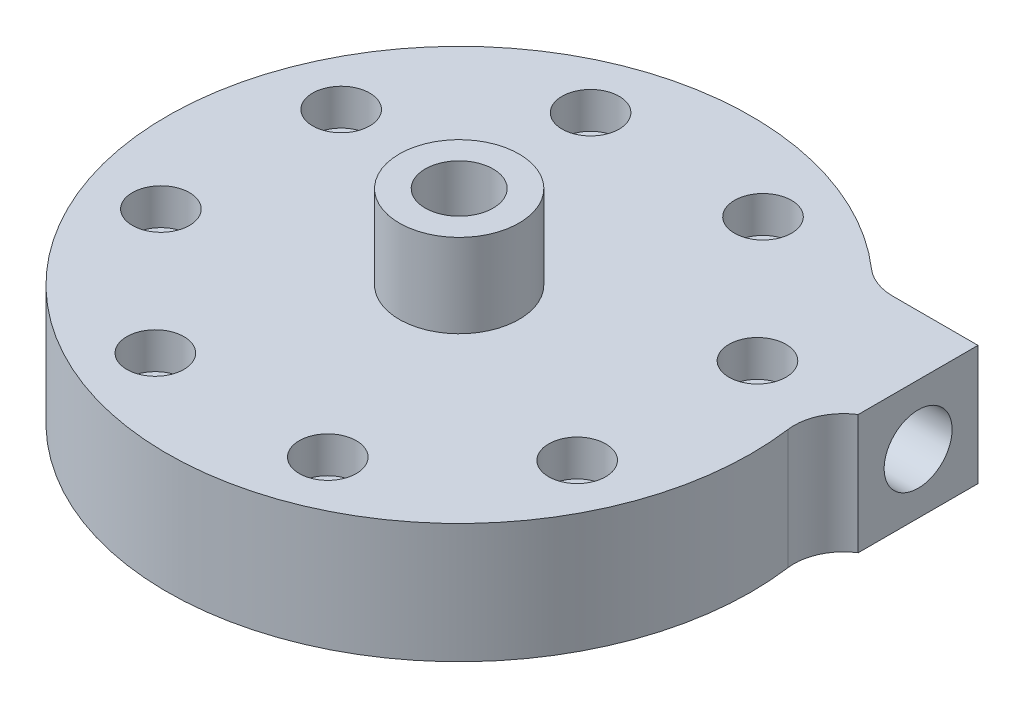
SolidWorks part; units mm, degrees
material "1060 Alloy"
ref_plane "Front" through (0, 0, 0) normal (0, 0, 1) x (1, 0, 0)
ref_plane "Top" through (0, 0, 0) normal (0, 1, 0) x (1, 0, 0)
ref_plane "Right" through (0, 0, 0) normal (1, 0, 0) x (0, 0, -1)
sketch "Sketch1" plane through (0, 0, 0) normal (0, 1, 0) x (1, 0, 0)
  line L0 (0, 0) -> (2.6731, 30.5538) construction
  line L1 (21.117, 30.6705) -> (50.1264, 33.2085) construction
  line L2 (11.6189, 28.3845) -> (50.1264, 28.3845) construction
  line L3 (21.117, 26.0945) -> (50.1264, 23.5565) construction
  line L4 (0, 0) -> (56.1418, -4.9118) construction
  line L5 (21.117, 30.6705) -> (21.117, 28.3845) construction
  line L6 (21.117, 28.3845) -> (21.117, 26.0945) construction
  line L7 (50.1264, 28.3845) -> (50.1264, 33.2085) construction
  line L8 (50.1264, 28.3845) -> (50.1264, 23.5565) construction
  line L9 (60.1264, 28.3845) -> (60.1264, 39.9329)
  line L10 (60.1264, 34.9329) -> (50.1264, 34.9329) construction
  line L11 (60.1264, 34.9329) -> (60.1264, 21.8361) construction
  line L12 (60.1264, 21.8361) -> (50.1264, 21.8361) construction
  line L13 (50.1264, 34.9329) -> (50.1264, 21.8361) construction
  line L14 (60.1264, 39.9329) -> (43.7019, 39.9329)
  line L15 (60.1264, 28.3845) -> (60.1264, 16.8361)
  line L17 (21.117, 30.6705) -> (0, 30.6705) construction
  line L18 (21.117, 26.0945) -> (16.117, 26.0945) construction
  arc A0 (37.1159, 42.408) -> (55.8478, 7.5534) centre (0, 0) ccw
  circle A1 centre (0, 0) radius 30.6705 construction
  arc A2 (55.8478, 7.5534) -> (60.1264, 16.8361) centre (65.2868, 8.8301) cw
  arc A3 (43.7019, 39.9329) -> (37.1159, 42.408) centre (43.7019, 49.9329) cw
  dimension "D1" = 112.7125
  dimension "D2" = 61.341
  dimension "D13" = 9.525
  dimension "D4" = 2.286
  dimension "D3" = 2.29
  dimension "D5" = 5
  dimension "D6" = 5
  dimension "D7" = 5
  dimension "D8" = 9.652
  dimension "D9" = 13.0969
  dimension "D10" = 10
  dimension "D11" = 5
  dimension "D14" = 5
  dimension "D12" = 5
extrude "main body" add sketch "Sketch1" along normal blind 23.0969
ref_plane "body midsection" through (0, 11.5484, 0) normal (0, 1, 0) x (1, 0, 0)
sketch "Sketch7" plane through (0, 23.0969, 0) normal (0, 1, 0) x (1, 0, 0)
  circle A0 centre (0, 0) radius 25.4
  dimension "D1" = 50.8
extrude "inlet boss" add sketch "Sketch7" along normal blind 50.8
sketch "Sketch3" plane through (0, 11.5484, 0) normal (0, 1, 0) x (1, 0, 0)
  line L0 (21.117, 30.6705) -> (0, 30.6705)
  line L1 (0, 30.6705) -> (0, 28.3845)
  line L2 (50.1264, 28.3845) -> (2.4833, 28.3845)
  line L3 (0, 0) -> (2.6731, 30.5538) construction
  line L4 (0, 28.3845) -> (2.4833, 28.3845)
  line L5 (50.1264, 33.2085) -> (50.1264, 34.9329)
  line L6 (50.1264, 34.9329) -> (60.1264, 34.9329)
  line L7 (60.1264, 34.9329) -> (60.1264, 28.3845)
  line L8 (60.1264, 28.3845) -> (50.1264, 28.3845)
  line L9 (21.117, 30.6705) -> (50.1264, 33.2085)
revolve "expansion cone and outlet" cut sketch "Sketch3" angle 360 about L2
sketch "Sketch2" plane through (0, 0, 0) normal (0, 0, 1) x (1, 0, 0)
  line L0 (-56.3562, 11.5484) -> (56.3562, 11.5484) construction
  line L1 (-56.3562, 23.0969) -> (-56.3562, 0) construction
  line L2 (56.3562, 0) -> (56.3562, 23.0969) construction
  line L3 (0, 0) -> (0, 23.0969) construction
  line L4 (25.4, 23.0969) -> (-25.4, 23.0969) construction
  line L5 (0, 18.6817) -> (0, 9.0936)
  line L6 (0, 9.0936) -> (26.67, 9.0936) construction
  line L7 (5.461, 18.6817) -> (5.565, 19.1708) construction
  line L8 (26.67, 14.1736) -> (5.461, 14.1736) construction
  line L9 (26.67, 9.0936) -> (26.67, 14.1736) construction
  line L10 (0, 19.1929) -> (0, 39.1929)
  line L11 (26.67, 14.1736) -> (5.461, 18.6817) construction
  line L12 (5.461, 18.6817) -> (0, 18.6817) construction
  line L13 (5.461, 18.6817) -> (5.461, 9.0936) construction
  line L14 (0, 9.0936) -> (0, 7.0936) construction
  line L15 (0, 7.0936) -> (26.67, 7.0936) construction
  line L16 (26.67, 7.0936) -> (26.67, 9.0936) construction
  line L17 (0, 9.0936) -> (0, 6.5936)
  line L18 (0, 7.0936) -> (0, 6.5936) construction
  line L19 (0, 6.5936) -> (26.67, 6.5936) construction
  line L20 (26.67, 6.5936) -> (26.67, 7.0936) construction
  line L21 (26.67, 6.5936) -> (30.6705, 6.5936) construction
  line L22 (30.6705, 6.5936) -> (30.6705, 13.3233)
  line L23 (26.67, 14.1736) -> (30.6705, 13.3233) construction
  line L24 (5.461, 18.6817) -> (5.461, 19.1929) construction
  line L25 (5.461, 19.1929) -> (0, 19.1929) construction
  line L26 (0, 19.1929) -> (0, 18.6817)
  line L27 (30.6705, 13.3233) -> (30.6705, 13.8344)
  line L28 (30.6705, 13.8344) -> (5.461, 19.1929)
  line L29 (0, 6.5936) -> (0, 0)
  line L30 (0, 0) -> (30.6705, 0)
  line L31 (-56.3562, 0) -> (56.3562, 0) construction
  line L32 (30.6705, 0) -> (30.6705, 6.5936)
  line L33 (30.6705, 13.8344) -> (0, 13.8344) construction
  line L34 (21.117, 13.8344) -> (0, 13.8344) construction
  line L35 (0, 39.1929) -> (6.5484, 39.1929) construction
  line L36 (6.5484, 39.1929) -> (6.5484, 29.1929)
  line L37 (6.5484, 29.1929) -> (5.461, 29.1929)
  line L38 (5.461, 29.1929) -> (5.461, 19.1929)
  line L39 (0, 39.1929) -> (0, 73.8969)
  line L40 (0, 73.8969) -> (25.4, 73.8969)
  line L41 (6.5484, 39.1929) -> (11.5484, 39.1929)
  line L42 (25.4, 73.8969) -> (-25.4, 73.8969) construction
  line L44 (11.5484, 39.1929) -> (11.5484, 23.0969)
  line L46 (25.4, 73.8969) -> (25.4, 23.0969)
  line L47 (25.4, 23.0969) -> (11.5484, 23.0969)
  dimension "D10" = 10
  dimension "D12" = 5
  dimension "D1" = 5.461
  dimension "D2" = 26.67
  dimension "D3" = 9.5881
  dimension "D4" = 5.08
  dimension "D5" = 2
  dimension "D6" = 4.0005
  dimension "D8" = 0.5
  dimension "D9" = 10
  dimension "D11" = 6.5484
revolve "main chamber" cut sketch "Sketch2" angle 360 about L5
sketch "Sketch5" plane through (0, 23.0969, 0) normal (0, 1, 0) x (1, 0, 0)
  line L1 (17.9206, 40.6775) -> (41.4351, 16.0915) construction
  line L3 (11.6189, 28.3845) -> (50.1264, 28.3845) construction
  circle A0 centre (0, 0) radius 44.45 construction
  circle A1 centre (41.4351, 16.0915) radius 2.9766
  circle A2 centre (0, 0) radius 44.45 construction
  circle A3 centre (40.6775, -17.9206) radius 2.9766
  circle A4 centre (0, 0) radius 44.45 construction
  circle A5 centre (16.0915, -41.4351) radius 2.9766
  circle A6 centre (0, 0) radius 44.45 construction
  circle A7 centre (-17.9206, -40.6775) radius 2.9766
  circle A8 centre (0, 0) radius 44.45 construction
  circle A9 centre (-41.4351, -16.0915) radius 2.9766
  circle A10 centre (0, 0) radius 44.45 construction
  circle A11 centre (-40.6775, 17.9206) radius 2.9766
  circle A12 centre (0, 0) radius 44.45 construction
  circle A13 centre (-16.0915, 41.4351) radius 2.9766
  circle A14 centre (0, 0) radius 44.45 construction
  circle A15 centre (17.9206, 40.6775) radius 2.9766
  point P5 (29.6778, 28.3845)
  point P30 (0, 0)
  dimension "D1" = 88.9
  dimension "D2" = 5.9531
  dimension "D4" = 8
sketch "Sketch6" plane through (0, 23.0969, 0) normal (0, 1, 0) x (1, 0, 0)
  circle A0 centre (41.4351, 16.0915) radius 5.5
  circle A1 centre (40.6775, -17.9206) radius 5.5
  circle A2 centre (16.0915, -41.4351) radius 5.5
  circle A3 centre (-17.9206, -40.6775) radius 5.5
  circle A4 centre (-41.4351, -16.0915) radius 5.5
  circle A5 centre (-40.6775, 17.9206) radius 5.5
  circle A6 centre (-16.0915, 41.4351) radius 5.5
  circle A7 centre (17.9206, 40.6775) radius 5.5
  point P19 (0, 0)
  dimension "D1" = 11
  dimension "D2" = 8
ref_plane "exit axial plane" through (0, 0, -28.3845) normal (0, 0, -1) x (-1, 0, 0)
extrude "bolt clearances" cut sketch "Sketch5" against normal through all
extrude "bolt head clearance" cut sketch "Sketch6" against normal blind 7
equation "\"bearing OD\"= 30mm"
equation "\"bearing ID\"= 10mm"
equation "\"bearing depth\"= 9mm"
equation "\"bearing outer race thickness\"= 1mm"
equation "\"bearing inner race thickness\"= 1mm"
equation "\"bearing bore\"= \"bearing depth\" + 1mm"
equation "\"z\"= 8\t\t\t\t'number of blades"
equation "\"de\"= 0.43in\t\t\t'entrance eye diameter"
equation "\"d2\"= 2.1in \t\t\t'outer diameter of the impeller"
equation "\"d_exit\"= 0.18in \t\t'throat aka d1"
equation "\"theta\"= 12\t\t\t'angle of blades from inner to outer "
equation "\"b2\"= .2in\t\t\t'tip height from disc surface at d2; slightly higher than d_exit"
equation "\"b1\"= \"b2\" + (\"d2\"/2 - \"de\"/2)*tan(\"theta\") \t\t\t'tip height from disc surface at inlet eye"
equation "\"s\"=\"ce\" - \"z\"*\"s_open\""
equation "\"impeller upper clearance\"= .5mm"
equation "\"impeller horizontal clearance\"= (\"d2\"*1.15 - \"d2\")/2 \t\t'clearance based on D2-D3 ratio for circular volute, ranges 1.15 to 1.2"
equation "\"impeller bottom clearance\"= .5mm"
equation "\"impeller base thickness\"= 2mm"
equation "\"impeller dowel diameter\"= 2mm"
equation "\"impeller bolt head diameter\"= \"m4 head bore diameter\""
equation "\"impeller bolt head depth\"= 4mm"
equation "\"impeller bolt stop depth\"= 3mm"
equation "\"impeller bolt bore\"= \"m4 clearance\""
equation "\"impeller shaft bore depth\"= 12mm"
equation "\"impeller shaft bore\"= 8mm"
equation "\"impeller boss depth\"= \"impeller shaft bore depth\"+\"impeller bolt stop depth\"+\"impeller bolt head depth\"-\"impeller base thickness\""
equation "\"impeller boss diameter\"= \"upper seal ID\""
equation "\"impeller dowel length\"= 2mm*2 + \"impeller shaft bore\""
equation "\"coupler motor shaft hole ID\"= 8mm"
equation "\"coupler OD\"= 17mm"
equation "\"coupler length\"= 25mm"
equation "\"motor OD\"= 64mm"
equation "\"motor shaft diameter\"= 8mm"
equation "\"motor shaft pride\"= 32mm"
equation "\"motor to bearing plate distance\"= \"motor shaft pride\" + 2mm +\"coupler length\"/2"
equation "\"square plate bolt bore\"= \"m8 clearance\""
equation "\"square plate bolt head diameter\"= 13.5mm"
equation "\"square plate bolt head depth\"= 8mm"
equation "\"square plate bolt pattern diameter\"= 3.5in"
equation "\"motor mount center bore\"= \"coupler OD\"+ 4mm"
equation "\"motor mount post radius\"= ( 3 * \"square plate bolt bore\" ) / 2"
equation "\"motor mount m4 screw hole diameter\"= 4mm"
equation "\"motor mount m4 head diameter\"= 7.25mm"
equation "\"motor mount m4 head depth\"= 4mm"
equation "\"motor mount m4 pattern diamater\"= 30mm"
equation "\"motor mount plate thickness\"= 8mm + \"motor mount m4 head depth\""
equation "\"bearing plate stop ID\"= \"bearing OD\" - 4mm"
equation "\"bearing plate stop depth\"= 3mm"
equation "\"bearing plate thickness\"= \"bearing bore\" + \"bearing plate stop depth\" + \"shaft bearing stop length\""
equation "\"shaft coupler section diameter\"= 8mm"
equation "\"shaft coupler section length\"= \"motor to bearing plate distance\" - \"motor shaft pride\" - 2mm"
equation "\"shaft bearing section diameter\"= \"bearing ID\""
equation "\"shaft bearing section length\"= \"bearing plate stop depth\" + \"bearing depth\""
equation "\"shaft bearing stop diameter\"= \"bearing ID\" + 4mm"
equation "\"shaft bearing stop length\"= 3mm"
equation "\"impeller cavity center height\"= \"impeller bottom clearance\" + \"impeller upper clearance\" + \"impeller center height\""
equation "\"impeller cavity diameter\"= 2 * \"impeller horizontal clearance\" + \"d2\" \t\t\t\t\t\t\t\t\t'called D3 analytically"
equation "\"impeller cavity outer height\"= \"impeller bottom clearance\" + \"impeller upper clearance\" + \"impeller base thickness\" + \"b2\" \t\t'this is height at impeller diameter d2, not at d3"
equation "\"impeller housing thickness\"= \"impeller housing exit threaded diameter\" + 2*\"impeller housing outlet grip\""
equation "\"impeller housing diameter\"= \"square plate bolt pattern diameter\" + 2*\"motor mount post radius\""
equation "\"impeller housing bolt count\"= 8"
equation "\"impeller housing bolt diameter\"= \"m6 clearance\""
equation "\"impeller housing bolt pattern diameter\"= 3.5in"
equation "\"impeller housing threaded inlet diameter\"= 0.515625in \t'this is the 33/64 drill size for 9/16-18 fitting, expecting swagelok SS-8FK0-1-6STH fitting"
equation "\"impeller housing threaded inlet depth\"= 10mm"
equation "\"impeller housing exit threaded diameter\"= 0.515625in \t\t'this is the 33/64 drill size for 9/16-18 fitting, expecting swagelok SS-8FK0-1-6STH fitting"
equation "\"impeller housing exit threaded depth\"= 10mm"
equation "\"impeller housing diffuser conical angle\"=10"
equation "\"impeller housing diffuser tangent angle\"=5"
equation "\"impeller housing diffuser final diameter\"= .38in\t\t'aka d2'"
equation "\"impeller housing outlet grip\"= 5mm"
equation "\"D1@Sketch1\"=\"impeller housing diameter\""
equation "\"D2@Sketch1\"=\"impeller cavity diameter\""
equation "\"D4@Sketch1\"=\"d_exit\"/2"
equation "\"D5@Sketch1\"=\"impeller housing diffuser tangent angle\""
equation "\"D6@Sketch1\"=\"impeller housing diffuser conical angle\"/2"
equation "\"D7@Sketch1\"=\"impeller housing diffuser conical angle\"/2"
equation "\"D8@Sketch1\"=\"impeller housing diffuser final diameter\""
equation "\"D9@Sketch1\"=\"impeller housing exit threaded diameter\""
equation "\"D10@Sketch1\"=\"impeller housing exit threaded depth\""
equation "\"D11@Sketch1\"=\"impeller housing outlet grip\""
equation "\"D1@main body\" = \"impeller housing thickness\""
equation "\"de_length\"= 10mm\t\t'entrance eye consistent length"
equation "\"D1@Sketch5\"=\"impeller housing bolt pattern diameter\""
equation "\"D2@Sketch5\"=\"m6 clearance\""
equation "\"end mill size\"= 0.375in\t'for 3/8 endmill"
equation "\"ae\"= 3.14*(\"de\"^2)/4\t\t'entrance eye area'"
equation "\"ce\"= 3.14*\"de\"\t\t'entrance eye circumference"
equation "\"av_ratio\"= .325\t\t'ratio of av/ae at N_s of 470, range is .275 to .375, .325 ideal. High ratio means bigger area means smaller blades"
equation "\"av\"= \"ae\"*\"av_ratio\"\t\t'area between just two blades"
equation "\"s_open\"= \"av\"/\"b1\"\t\t'width of open area"
equation "\"impeller center height\"= \"impeller base thickness\" + \"b1\"\t'impeller height at de"
equation "\"impeller outer height\"= \"impeller base thickness\" + \"b2\"\t'impeller height at de"
equation "\"shaft impeller section diameter\"= \"impeller shaft bore\""
equation "\"shaft impeller section length\"= \"upper seal plate thickness\" + \"upper seal plate riser\" + \"impeller bottom clearance\" + \"impeller base thickness\" - \"impeller bolt head depth\" - \"impeller bolt stop depth\""
equation "\"m6 clearance\"= 0.234375in\t'this is 15/64 bit = 5.95mm, could use 6mm bit, B bit for 6.04mm or 1/4 bit for 6.35mm"
equation "\"m6 tap\"= 5mm\t\t\t'5mm is appropriate, could use 13/64 or #5,6,7"
equation "\"m6 head bore diameter\"= 11mm\t\t"
equation "\"m6 head bore depth\"= 7mm\t'actual is 6mm"
equation "\"m8 clearance\"= 0.3125in\t'this is 5/16in for 7.93mm, could use 8mm, O,P, or 21/64"
equation "\"m8 tap\"= 0.265625in\t\t'this is 17/64 for 6.746875mm"
equation "\"m8 head bore diameter\"= 14mm"
equation "\"m8 head bore depth\"= 9mm\t'actual is 8mm"
equation "\"D1@Sketch6\"=\"m6 head bore diameter\""
equation "\"D1@bolt head clearance\" = \"m6 head bore depth\""
equation "\"lower seal OD\"= .917in\t\t'this is https://www.mcmaster.com/#9281k121/=174001b"
equation "\"lower seal ID\"= .375in"
equation "\"lower seal depth\"= .625in + .218in"
equation "\"lower seal bore\"= \"lower seal depth\" + 1mm"
equation "\"upper seal OD\"= 1.125in\t'this is https://www.mcmaster.com/#5154t33/=173zuau, needs to be visually inspected before machining!"
equation "\"upper seal ID\"= 0.625in"
equation "\"upper seal depth\"= .25in\t'aka height; these values need to be confirmed by inspection!! We may want to compress the height."
equation "\"upper seal bore\"= \"upper seal depth\" + 1mm"
equation "\"big o-ring thickness\"= .139in"
equation "\"big o-ring OD\"= 2.734in"
equation "\"big o-ring ID\"= 3.012in"
equation "\"big o-ring groove depth\"= \"big o-ring thickness\"*4/5"
equation "\"lower seal plate lip depth\"= 2mm"
equation "\"lower seal plate lip ID\"= \"lower seal OD\" - 3mm"
equation "\"lower seal plate thickness\"= \"lower seal plate lip depth\" + \"lower seal bore\""
equation "\"shaft lower seal section diameter\"= \"lower seal ID\""
equation "\"shaft lower seal section length\"= \"lower seal plate thickness\" + 1mm"
equation "\"upper seal plate thickness\"= \"upper seal plate pressure hole diameter\"+10mm"
equation "\"upper seal plate lip ID\"= \"upper seal OD\" - 3mm"
equation "\"upper seal plate riser\"= 6.59mm \t\t'this number needs to be read from the housing file"
equation "\"upper seal plate pressure hole diameter\"= .125in\t'this is 1/8 drill "
equation "\"upper seal plate pressure tap diameter\"= .328125in \t'this is 21/64 drill for a 1/8 ANPT tap"
equation "\"upper seal plate pressure tap grip\"= 5mm\t\t'this is the area around the tap so it doesn't crack"
equation "\"upper seal plate pressure tap depth\"= 12"
equation "\"m4 clearance\"= 0.171875in \t'this is 11/64 bit for 4.36mm"
equation "\"m4 tap\"= 0.125in\t\t'this is 1/8 bit for 3.17mm"
equation "\"m4 head bore diameter\"= 7.5mm"
equation "\"m4 head bore depth\"= 5mm\t'actual is ~4mm"
equation "\"D1@Sketch2\"=\"de\"/2"
equation "\"D3@Sketch2\"=\"b1\""
equation "\"D4@Sketch2\"=\"b2\""
equation "\"D2@Sketch2\"=\"d2\"/2"
equation "\"D5@Sketch2\"=\"impeller base thickness\""
equation "\"D6@Sketch2\"=\"impeller horizontal clearance\""
equation "\"D7@Sketch2\"=\"impeller bottom clearance\""
equation "\"D8@Sketch2\"=\"impeller upper clearance\""
equation "\"D9@Sketch2\"=\"de_length\""
equation "\"D10@Sketch2\"=\"impeller housing threaded inlet depth\""
equation "\"D11@Sketch2\"=\"impeller housing threaded inlet diameter\"/2"
equation "\"D12@Sketch2\"=\"impeller housing outlet grip\""
equation "\"min blade thickness\"= .15in"
equation "\"l_exit\"= 5mm\t\t\t'length of eye entrance"
equation "\"D12@Sketch1\"=\"impeller housing outlet grip\""
equation "\"D13@Sketch1\"=\"end mill size\""
